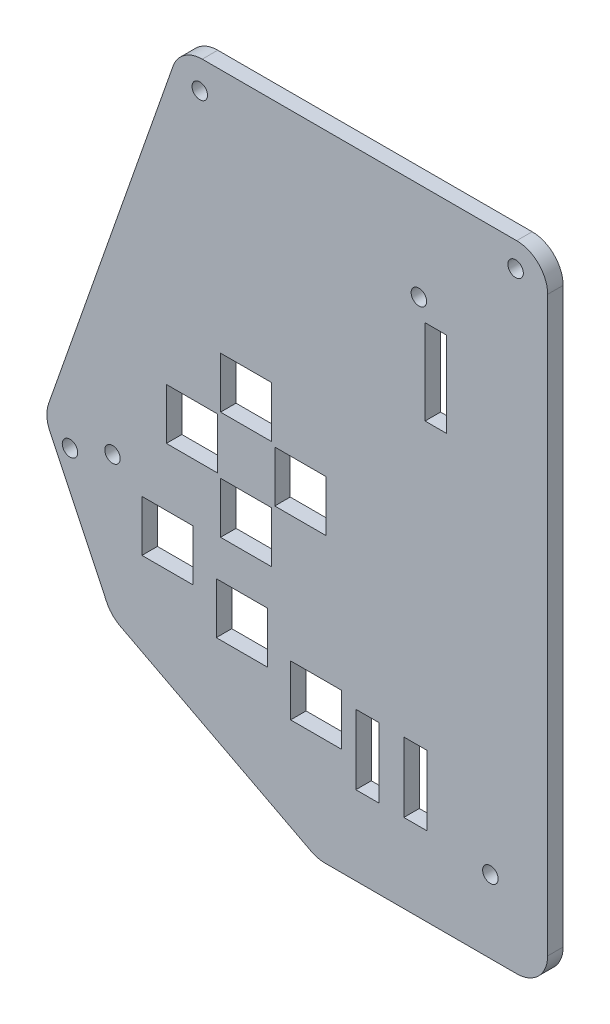
SolidWorks part; units mm, degrees
ref_plane "Front Plane" through (0, 0, 0) normal (0, 0, 1) x (1, 0, 0)
ref_plane "Top Plane" through (0, 0, 0) normal (0, 1, 0) x (1, 0, 0)
ref_plane "Right Plane" through (0, 0, 0) normal (1, 0, 0) x (0, 0, -1)
sketch "Sketch1" plane through (0, 0, 0) normal (0, 0, 1) x (1, 0, 0)
  line L6 (-20.066, -57.15) -> (46.99, -57.15) construction
  line L7 (-12.446, -73.152) -> (46.99, -73.152) construction
  line L8 (-3.3141, 6.35) -> (48.26, 6.35)
  line L9 (53.34, 1.27) -> (53.34, -92.71)
  line L10 (48.26, -97.79) -> (16.847, -97.79)
  line L16 (-8.1072, 2.9529) -> (-28.5162, -55.1739)
  line L18 (-20.066, -57.15) -> (-29.21, -57.15) construction
  line L26 (0, 0) -> (46.99, 0) construction
  line L27 (46.99, 0) -> (46.99, -88.9) construction
  line L28 (46.99, -88.9) -> (17.78, -88.9) construction
  line L29 (17.78, -88.9) -> (-12.446, -73.152) construction
  line L30 (-12.446, -73.152) -> (-20.066, -57.15) construction
  line L31 (-20.066, -57.15) -> (0, 0) construction
  line L32 (46.99, -57.15) -> (46.99, -88.9) construction
  line L33 (17.78, -88.9) -> (15.603, -97.79) construction
  line L34 (-12.446, -73.152) -> (-17.9301, -78.4424) construction
  line L35 (14.4997, -97.2152) -> (-16.7505, -80.9336)
  line L36 (-28.3096, -59.0409) -> (-18.9898, -78.6124)
  arc A0 (53.34, -92.71) -> (48.26, -97.79) centre (48.26, -92.71) cw
  arc A1 (14.4997, -97.2152) -> (16.847, -97.79) centre (16.847, -92.71) ccw
  arc A2 (-16.7505, -80.9336) -> (-18.9898, -78.6124) centre (-14.4033, -76.4284) cw
  arc A3 (-28.5162, -55.1739) -> (-28.3096, -59.0409) centre (-23.723, -56.8568) ccw
  arc A4 (-8.1072, 2.9529) -> (-3.3141, 6.35) centre (-3.3141, 1.27) cw
  arc A5 (48.26, 6.35) -> (53.34, 1.27) centre (48.26, 1.27) cw
  point P13 (53.34, -97.79)
  point P32 (53.34, 6.35)
  dimension "D8" = 5.08
  dimension "D1" = 88.9
  dimension "D2" = 29.21
  dimension "D3" = 59.436
  dimension "D4" = 67.056
  dimension "D5" = 104.14
  dimension "D6" = 82.55
  dimension "D7" = 46.99
  dimension "D13" = 103.76
  dimension "D17" = 108.51
sketch "Sketch3" plane through (0, 0, 0) normal (0, 0, 1) x (1, 0, 0)
  line L6 (-20.066, -57.15) -> (46.99, -57.15) construction
  line L7 (-12.446, -73.152) -> (46.99, -73.152) construction
  line L8 (0, 0) -> (46.99, 0) construction
  line L9 (46.99, 0) -> (46.99, -88.9) construction
  line L10 (46.99, -88.9) -> (17.78, -88.9) construction
  line L11 (17.78, -88.9) -> (-12.446, -73.152) construction
  line L12 (-12.446, -73.152) -> (-20.066, -57.15) construction
  line L13 (-20.066, -57.15) -> (0, 0) construction
  line L14 (3.8784, -55.88) -> (3.8784, -38.1) construction
  circle A0 centre (3.8784, -38.1) radius 5.08
  circle A1 centre (-5.0116, -46.99) radius 5.08
  circle A2 centre (3.8784, -55.88) radius 5.08
  circle A3 centre (12.7684, -46.99) radius 5.08
  circle A4 centre (-9.144, -65.024) radius 5.08
  circle A5 centre (3.048, -70.612) radius 5.08
  circle A6 centre (15.24, -76.2) radius 5.08
  dimension "D7" = 10.16
  dimension "D1" = 43.1116
  dimension "D2" = 8.89
  dimension "D3" = 8.89
  dimension "D4" = 46.99
  dimension "D5" = 8.89
  dimension "D6" = 8.89
  dimension "D8" = 12.192
  dimension "D9" = 5.588
  dimension "D10" = 5.588
  dimension "D11" = 12.192
  dimension "D12" = 43.942
  dimension "D13" = 70.612
sketch "Sketch10" plane through (0, 0, 0) normal (0, 0, 1) x (1, 0, 0)
  line L1 (53.34, 1.27) -> (53.34, -92.71)
  line L6 (48.26, -97.79) -> (16.847, -97.79)
  line L16 (-8.1072, 2.9529) -> (-28.5162, -55.1739)
  line L19 (53.34, 1.27) -> (53.34, -92.71) construction
  line L21 (-8.1072, 2.9529) -> (-28.5162, -55.1739) construction
  line L24 (14.4997, -97.2152) -> (-16.7505, -80.9336)
  line L25 (-18.9898, -78.6124) -> (-28.3096, -59.0409)
  line L26 (-3.3141, 6.35) -> (48.26, 6.35)
  arc A0 (-18.9898, -78.6124) -> (-16.7505, -80.9336) centre (-14.4033, -76.4284) ccw
  arc A1 (16.847, -97.79) -> (14.4997, -97.2152) centre (16.847, -92.71) cw
  arc A2 (-28.5162, -55.1739) -> (-28.3096, -59.0409) centre (-23.723, -56.8568) ccw
  arc A3 (53.34, -92.71) -> (48.26, -97.79) centre (48.26, -92.71) cw
  arc A4 (-8.1072, 2.9529) -> (-3.3141, 6.35) centre (-3.3141, 1.27) cw
  arc A5 (48.26, 6.35) -> (53.34, 1.27) centre (48.26, 1.27) cw
  point P13 (15.603, -97.79)
  point P17 (-29.21, -57.15)
  point P20 (53.34, -97.79)
  dimension "D1" = 5.08
extrude "Boss-Extrude1" add sketch "Sketch10" along normal blind 2.54
sketch "Sketch11" plane through (0, 0, 2.54) normal (0, 0, 1) x (1, 0, 0)
  line L0 (46.99, -88.9) -> (17.78, -88.9) construction
  line L5 (33.561, -73.406) -> (29.751, -73.406)
  line L6 (33.561, -73.406) -> (33.561, -84.836)
  line L11 (33.561, -84.836) -> (29.751, -84.836)
  line L12 (29.751, -73.406) -> (29.751, -84.836)
  line L18 (46.99, 0) -> (46.99, -88.9) construction
  line L23 (25.687, -73.406) -> (21.877, -73.406)
  line L24 (25.687, -73.406) -> (25.687, -84.836)
  line L29 (25.687, -84.836) -> (21.877, -84.836)
  line L30 (21.877, -73.406) -> (21.877, -84.836)
  line L42 (8.0694, -51.689) -> (-0.3126, -51.689)
  line L43 (8.0694, -51.689) -> (8.0694, -60.071)
  line L44 (8.0694, -60.071) -> (-0.3126, -60.071)
  line L45 (-0.3126, -51.689) -> (-0.3126, -60.071)
  line L46 (-0.8206, -42.799) -> (-9.2026, -42.799)
  line L47 (-0.8206, -42.799) -> (-0.8206, -51.181)
  line L48 (-0.8206, -51.181) -> (-9.2026, -51.181)
  line L49 (-9.2026, -42.799) -> (-9.2026, -51.181)
  line L52 (8.0694, -42.291) -> (-0.3126, -42.291)
  line L53 (-0.3126, -33.909) -> (-0.3126, -42.291)
  line L54 (16.9594, -42.799) -> (8.5774, -42.799)
  line L55 (16.9594, -42.799) -> (16.9594, -51.181)
  line L56 (16.9594, -51.181) -> (8.5774, -51.181)
  line L57 (8.5774, -42.799) -> (8.5774, -51.181)
  line L58 (-0.3126, -33.909) -> (8.0694, -33.909)
  line L59 (8.0694, -33.909) -> (8.0694, -42.291)
  line L60 (3.8784, -51.689) -> (3.8784, -60.071) construction
  line L61 (-0.3126, -55.88) -> (8.0694, -55.88) construction
  line L62 (-5.0116, -51.181) -> (-5.0116, -42.799) construction
  line L63 (-9.2026, -46.99) -> (-0.8206, -46.99) construction
  line L64 (12.7684, -42.799) -> (12.7684, -51.181) construction
  line L65 (8.5774, -46.99) -> (16.9594, -46.99) construction
  line L66 (3.8784, -33.909) -> (3.8784, -42.291) construction
  line L67 (-0.3126, -38.1) -> (8.0694, -38.1) construction
  line L68 (-4.826, -60.706) -> (-4.826, -69.088)
  line L69 (-13.208, -65.024) -> (-5.08, -65.024) construction
  line L70 (-9.144, -60.96) -> (-9.144, -69.088) construction
  line L71 (-4.826, -69.088) -> (-13.208, -69.088)
  line L72 (-13.208, -60.706) -> (-13.208, -69.088)
  line L73 (-4.826, -60.706) -> (-13.208, -60.706)
  line L74 (7.366, -66.294) -> (7.366, -74.676)
  line L75 (-1.016, -70.612) -> (7.112, -70.612) construction
  line L76 (3.048, -66.548) -> (3.048, -74.676) construction
  line L77 (7.366, -74.676) -> (-1.016, -74.676)
  line L78 (-1.016, -66.294) -> (-1.016, -74.676)
  line L79 (7.366, -66.294) -> (-1.016, -66.294)
  line L80 (19.558, -71.882) -> (19.558, -80.264)
  line L81 (11.176, -76.2) -> (19.304, -76.2) construction
  line L82 (15.24, -72.136) -> (15.24, -80.264) construction
  line L83 (19.558, -80.264) -> (11.176, -80.264)
  line L84 (11.176, -71.882) -> (11.176, -80.264)
  line L85 (19.558, -71.882) -> (11.176, -71.882)
  dimension "D1" = 4.064
  dimension "D3" = 13.429
  dimension "D4" = 11.43
  dimension "D5" = 3.81
  dimension "D6" = 4.064
  dimension "D7" = 11.43
  dimension "D8" = 4.064
  dimension "D9" = 3.81
  dimension "D10" = 2.319
  dimension "D11" = 3.81
  dimension "D12" = 6.223
  dimension "D13" = 3.81
  dimension "D14" = 5.588
  dimension "D15" = 8.382
  dimension "D16" = 2.794
  dimension "D17" = 0.508
  dimension "D18" = 0.508
  dimension "D21" = 8.382
  dimension "D22" = 8.382
extrude "Cut-Extrude1" cut sketch "Sketch11" against normal through all both and the other way through all
sketch "Sketch12" plane through (0, 0, 0) normal (0, 0, -1) x (-1, 0, 0)
  line L0 (20.066, -57.15) -> (-46.99, -57.15) construction
  line L2 (-46.99, 0) -> (-46.99, -88.9) construction
  line L5 (18.034, -57.15) -> (20.066, -57.15) construction
  line L10 (-46.99, -88.9) -> (-17.78, -88.9) construction
  circle A2 centre (18.034, -57.15) radius 1.27
  circle A3 centre (-43.942, -85.852) radius 1.27
  dimension "D1" = 2.54
  dimension "D6" = 2.032
  dimension "D2" = 2.54
  dimension "D11" = 3.048
  dimension "D12" = 3.048
extrude "Cut-Extrude2" cut sketch "Sketch12" against normal through all both and the other way through all
sketch "Sketch13" plane through (0, 0, 0) normal (0, 0, -1) x (-1, 0, 0)
  line L0 (28.3096, -59.0409) -> (18.9898, -78.6124) construction
  line L1 (8.1072, 2.9529) -> (28.5162, -55.1739) construction
  line L2 (3.3141, 6.35) -> (-48.26, 6.35) construction
  line L4 (-53.34, 1.27) -> (-53.34, -92.71) construction
  circle A1 centre (25.0123, -59.762) radius 1.27
  circle A4 centre (-48.0822, 2.286) radius 1.27
  circle A5 centre (3.7187, 1.651) radius 1.27
  dimension "D1" = 2.54
  dimension "D2" = 4.826
  dimension "D4" = 4.064
  dimension "D3" = 2.667
  dimension "D5" = 5.2578
  dimension "D6" = 4.699
  dimension "D7" = 4.572
extrude "Cut-Extrude3" cut sketch "Sketch13" against normal through all both and the other way through all
sketch "Sketch14" plane through (0, 0, 0) normal (0, 0, -1) x (-1, 0, 0)
  line L0 (-36.7885, -26.7831) -> (-33.2325, -26.7831)
  line L1 (-36.7885, -12.8131) -> (-36.7885, -26.7831)
  line L2 (-33.2325, -12.8131) -> (-36.7885, -12.8131)
  line L3 (-33.2325, -12.8131) -> (-33.2325, -26.7831)
  line L4 (-53.34, 1.27) -> (-53.34, -92.71) construction
  line L5 (3.3141, 6.35) -> (-48.26, 6.35) construction
  dimension "D1" = 16.5515
  dimension "D2" = 13.97
  dimension "D3" = 19.1631
  dimension "D4" = 3.556
extrude "Cut-Extrude4" cut sketch "Sketch14" against normal through all both and the other way through all
sketch "Sketch16" plane through (0, 0, 0) normal (0, 0, -1) x (-1, 0, 0)
  line L0 (3.3141, 6.35) -> (-48.26, 6.35) construction
  line L1 (-53.34, 1.27) -> (-53.34, -92.71) construction
  circle A0 centre (-32.219, -9.6761) radius 1.27
  dimension "D1" = 16.0261
  dimension "D2" = 2.54
  dimension "D3" = 21.121
extrude "Cut-Extrude5" cut sketch "Sketch16" against normal through all both and the other way through all
